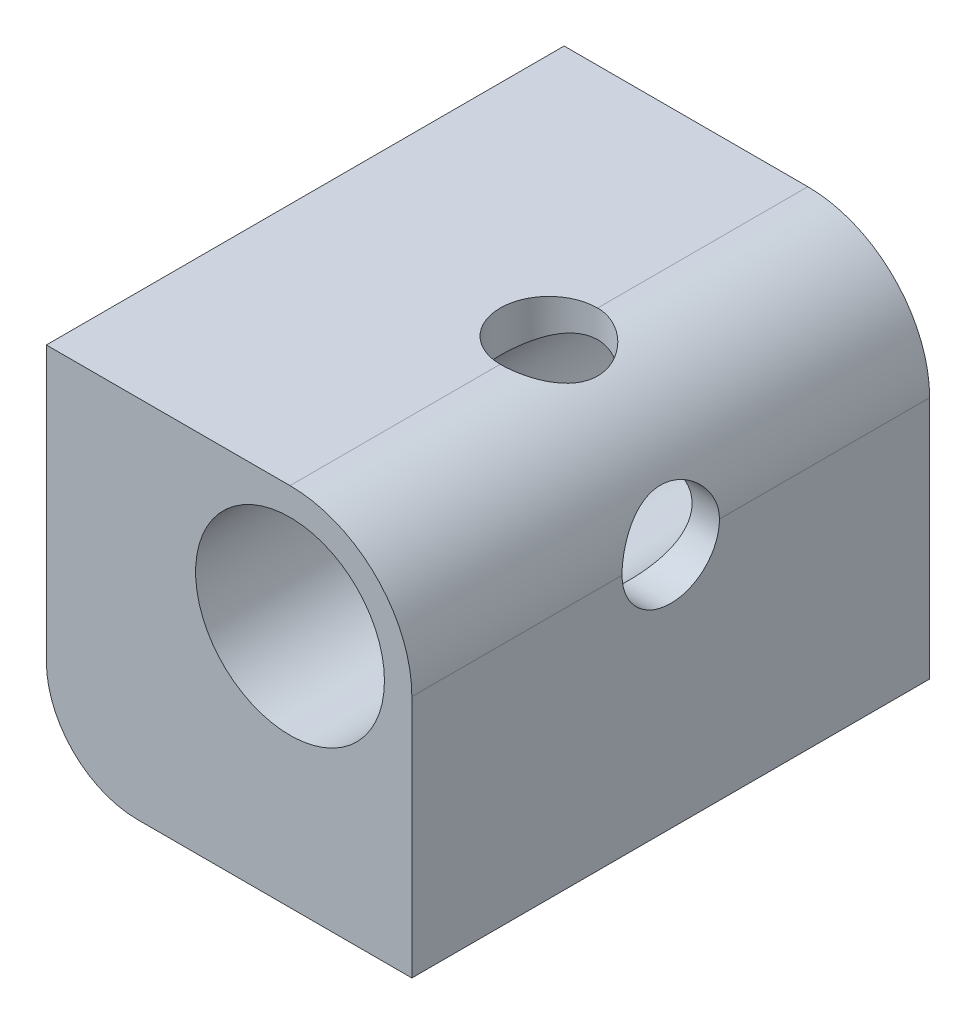
SolidWorks part; units mm, degrees
ref_plane "正面" through (0, 0, 0) normal (0, 0, 1) x (1, 0, 0)
ref_plane "平面" through (0, 0, 0) normal (0, 1, 0) x (1, 0, 0)
ref_plane "右側面" through (0, 0, 0) normal (1, 0, 0) x (0, 0, -1)
sketch "ｽｹｯﾁ1" plane through (0, 0, 0) normal (0, 0, 1) x (1, 0, 0)
  line L1 (-7, -7) -> (7, -7)
  line L2 (-7, -7) -> (-7, 7)
  line L3 (-7, 7) -> (7, 7)
  line L4 (7, -7) -> (7, 7)
  line L5 (-7, -7) -> (7, 7) construction
  line L6 (-7, 7) -> (7, -7) construction
  point P0 (0, 0)
  dimension "D1" = 14
  dimension "D2" = 14
extrude "ﾎﾞｽ - 押し出し1" add sketch "ｽｹｯﾁ1" along normal blind 17
sketch "ｽｹｯﾁ2" plane through (0, 0, 17) normal (0, 0, 1) x (1, 0, 0)
  line L0 (-7, 7) -> (-7, -7) construction
  line L1 (7, 7) -> (-7, 7) construction
  circle A0 centre (3, 3) radius 3.1
  dimension "D1" = 10
  dimension "D2" = 4
  dimension "D3" = 6.2
extrude "ｶｯﾄ - 押し出し1" cut sketch "ｽｹｯﾁ2" against normal through all
fillet "ﾌｨﾚｯﾄ1" radius 5 1 edges at (-7, -7, 8.5)
sketch "ｽｹｯﾁ3" plane through (0, 0, 17) normal (0, 0, 1) x (1, 0, 0)
  line L0 (-7, 7) -> (-7, -7)
  line L1 (-7, -7) -> (7, -7)
  line L2 (7, -7) -> (7, -5)
  line L8 (-5, 7) -> (-7, 7)
  line L10 (-2, -5) -> (7, -5)
  line L11 (-5, 7) -> (-5, -2)
  line L12 (-2, -5) -> (7, -5)
  line L13 (-5, 7) -> (-5, -2)
  arc A4 (-5, -2) -> (-2, -5) centre (-2, -2) ccw
  arc A5 (-5, -2) -> (-2, -5) centre (-2, -2) ccw
  dimension "D1" = 2
extrude "ｶｯﾄ - 押し出し2" cut sketch "ｽｹｯﾁ3" against normal blind 17
sketch "ｽｹｯﾁ4" plane through (0, -5, 0) normal (0, -1, 0) x (1, 0, 0)
  line L0 (7, 17) -> (-2, 17) construction
  line L1 (7, 0) -> (7, 17) construction
  circle A0 centre (3, 8.5) radius 1.6
  dimension "D2" = 4
  dimension "D3" = 3.2
  dimension "D1" = 8.5
extrude "ｶｯﾄ - 押し出し3" cut sketch "ｽｹｯﾁ4" against normal blind 17
sketch "ｽｹｯﾁ5" plane through (-5, 0, 0) normal (-1, 0, 0) x (0, 0, 1)
  line L0 (0, 7) -> (17, 7) construction
  line L1 (17, -2) -> (17, 7) construction
  circle A0 centre (8.5, 3) radius 1.6
  dimension "D2" = 8.5
  dimension "D3" = 3.2
  dimension "D1" = 4
extrude "ｶｯﾄ - 押し出し4" cut sketch "ｽｹｯﾁ5" against normal blind 17
fillet "ﾌｨﾚｯﾄ2" radius 4 1 edges at (7, 7, 8.5)
